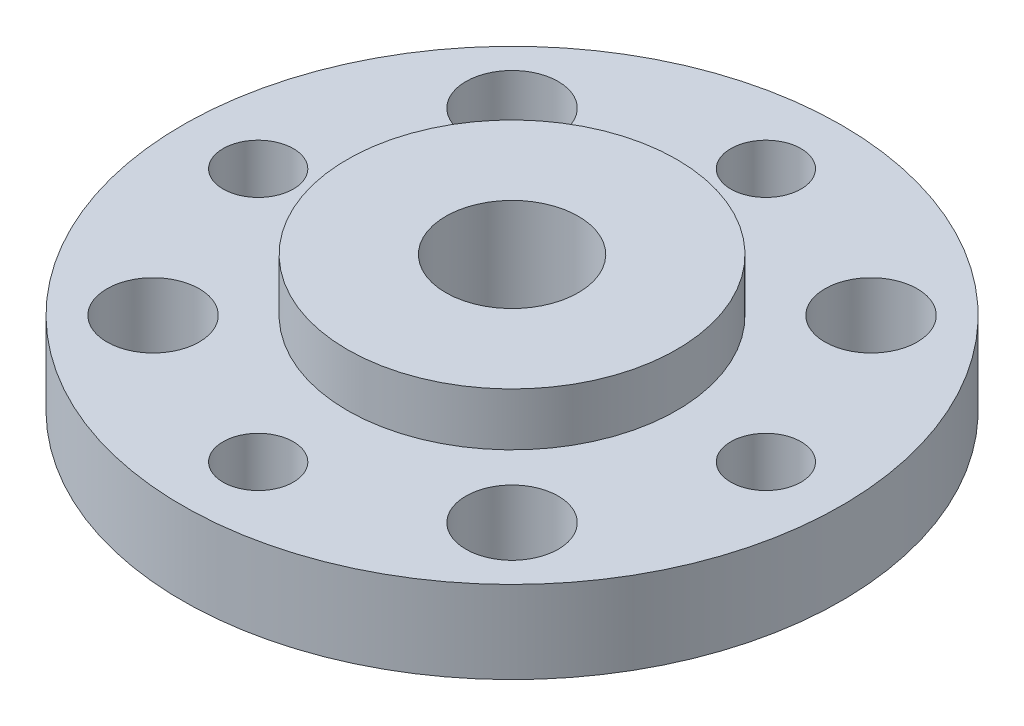
SolidWorks part; units mm, degrees
ref_plane "Front Plane" through (0, 0, 0) normal (0, 0, 1) x (1, 0, 0)
ref_plane "Top Plane" through (0, 0, 0) normal (0, 1, 0) x (1, 0, 0)
ref_plane "Right Plane" through (0, 0, 0) normal (1, 0, 0) x (0, 0, -1)
sketch "Sketch1" plane through (0, 0, 0) normal (0, 0, 1) x (1, 0, 0)
  line L0 (12.6962, 3.175) -> (0, 3.175)
  line L1 (0, 3.175) -> (0, 0)
  line L2 (0, 0) -> (12.6962, 0)
  line L3 (12.6962, 0) -> (12.6962, 3.175)
  line L4 (0, 3.175) -> (0, 0) construction
revolve "Revolve1" add sketch "Sketch1" angle 360 about L4 reverse direction yes
sketch "Sketch2" plane through (0, 3.175, 0) normal (0, 1, 0) x (-1, 0, 0)
  circle A0 centre (0, 0) radius 6.3462
extrude "Boss-Extrude1" add sketch "Sketch2" along normal blind 2.032
hole_wizard "M2.5 Clearance Hole1" positions "Sketch4" profile "Sketch3" hole size "M2.5" standard "ANSI Metric"
sketch "Sketch4" plane through (0, 3.175, 0) normal (0, 1, 0) x (1, 0, 0)
  point P0 (-9.779, 0)
  point P1 (0, 9.779)
  point P2 (9.779, 0)
  point P3 (0, -9.779)
sketch "Sketch3" plane through (-9.779, 3.175, 0) normal (1, 0, 0) x (0, 0, 1)
  line L0 (0, 0) -> (0, 3.175)
  line L1 (0, 3.175) -> (1.3525, 3.175)
  line L2 (1.3525, 3.175) -> (1.3525, 0)
  line L5 (1.3525, 0) -> (0, 0)
  line L11 (0, -6.35) -> (0, 107.95) construction
  dimension "Thru Hole Dia." = 2.7051
  dimension "Thru Hole Depth" = 3.175
hole_wizard "Hole1" positions "Sketch6" profile "Sketch5" legacy
sketch "Sketch6" plane through (0, 5.207, 0) normal (0, 1, 0) x (1, 0, 0)
  point P0 (0, 0)
sketch "Sketch5" plane through (0, 5.207, 0) normal (1, 0, 0) x (0, 0, 1)
  line L0 (0, 0) -> (0, 5.207)
  line L1 (0, 5.207) -> (2.5527, 5.207)
  line L2 (2.5527, 5.207) -> (2.5527, 0)
  line L3 (2.5527, 0) -> (0, 0)
  line L4 (0, 110) -> (0, -10) construction
  dimension "Diameter" = 5.1054
  dimension "Depth" = 5.207
hole_wizard "M3 Clearance Hole1" positions "Sketch8" profile "Sketch7" hole size "M3" standard "ANSI Metric"
sketch "Sketch8" plane through (0, 0, 0) normal (0, -1, 0) x (-1, 0, 0)
  point P0 (6.9148, 6.9148)
  point P1 (-6.9148, 6.9148)
  point P2 (-6.9148, -6.9148)
  point P3 (6.9148, -6.9148)
sketch "Sketch7" plane through (-6.9148, 0, -6.9148) normal (1, 0, 0) x (0, 0, -1)
  line L0 (0, 0) -> (0, 5.207)
  line L1 (0, 5.207) -> (1.778, 5.207)
  line L2 (1.778, 5.207) -> (1.778, 0)
  line L5 (1.778, 0) -> (0, 0)
  line L11 (0, -6.35) -> (0, 107.95) construction
  dimension "Thru Hole Dia." = 3.556
  dimension "Thru Hole Depth" = 5.207
